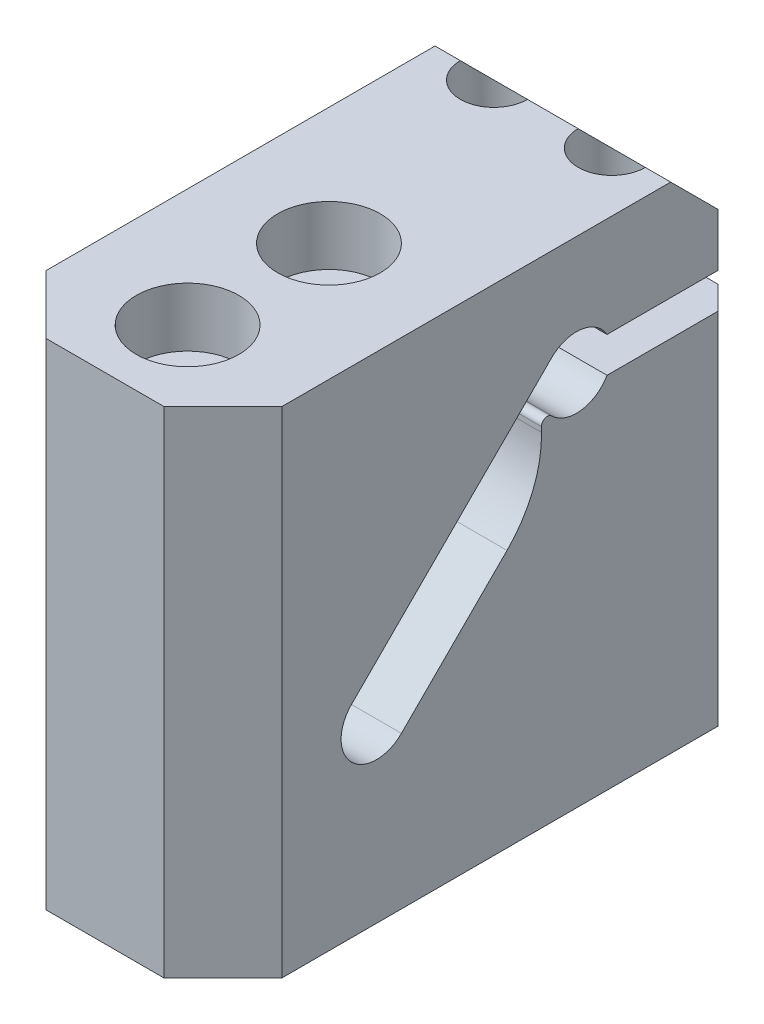
SolidWorks part; units mm, degrees
ref_plane "정면" through (0, 0, 0) normal (0, 0, 1) x (1, 0, 0)
ref_plane "윗면" through (0, 0, 0) normal (0, 1, 0) x (1, 0, 0)
ref_plane "우측면" through (0, 0, 0) normal (1, 0, 0) x (0, 0, -1)
sketch "스케치1" plane through (0, 0, 0) normal (1, 0, 0) x (0, 0, -1)
  line L0 (0, 0) -> (0, -32) construction
  line L1 (-19.0919, -14.8492) -> (-14.8492, -19.0919)
  line L2 (14, -32) -> (-30, -32)
  line L3 (14, -32) -> (14, 4)
  line L4 (8, 10) -> (-30, 10)
  line L5 (-30, -32) -> (-30, 10)
  line L6 (-19.0919, -14.8492) -> (-2.1213, 2.1213)
  line L7 (-14.8492, -19.0919) -> (2.1213, -2.1213)
  line L8 (-2.1213, 2.1213) -> (2.1213, -2.1213)
  line L9 (14, 4) -> (8, 10)
  line L10 (0, 0) -> (14, 0) construction
  line L11 (14, 1.5) -> (1, 1.5)
  line L12 (14, 1.5) -> (14, -1.5)
  line L13 (14, -1.5) -> (1, -1.5)
  line L14 (1, 1.5) -> (1, -1.5)
  line L15 (-3, 0) -> (-2.9035, -7.1461)
  circle A0 centre (0, 0) radius 3
  arc A1 (-19.0919, -14.8492) -> (-14.8492, -19.0919) centre (-16.9706, -16.9706) ccw
  point P6 (14, 10)
  dimension "D1" = 6
  dimension "D2" = 32
  dimension "D3" = 10
  dimension "D4" = 6
  dimension "D5" = 45
  dimension "D6" = 14
  dimension "D7" = 24
  dimension "D9" = 3
  dimension "D10" = 13
  dimension "D11" = 44
extrude "보스-돌출1" add sketch "스케치1" along normal blind 20 contours A1 L6 A0 L11 L3 L9 L4 L5 L2 L13 L7 | A0 L15 L7 region at (0, -19.522, 19.522) region at (0, -3.9996, 1.6249)
fillet "필렛1" radius 10 1 edges at (10, -7.1461, 2.9035)
fillet "필렛2" radius 0.5 1 edges at (10, -0.081, 2.9989)
sketch "스케치2" plane through (0, 10, 0) normal (0, 1, 0) x (1, 0, 0)
  line L0 (10, 14) -> (10, -30) construction
  line L1 (20, 14) -> (0, 14) construction
  line L2 (20, -30) -> (0, -30) construction
  circle A0 centre (10, -23) radius 4.35
  circle A1 centre (10, -11) radius 4.35
  circle A3 centre (5, 8) radius 1.5
  circle A4 centre (15, 8) radius 1.5
  circle A5 centre (5, 8) radius 2.85
  circle A6 centre (15, 8) radius 2.85
  circle A7 centre (10, -11) radius 2.5
  circle A8 centre (10, -23) radius 2.5
  point P18 (0, 0)
  line M11 (20, 8) -> (0, 8)
  dimension "D1" = 3
  dimension "D4" = 5.7
  dimension "D5" = 8.7
  dimension "D6" = 5
  dimension "D2" = 6
  dimension "D3" = 5
  dimension "D7" = 12
  dimension "D8" = 7
extrude "컷-돌출1" cut sketch "스케치2" against normal blind 5 contours L0 A1 A7 | A1 L0 A7 | A0 L0 A8 | L0 A0 A8 region at (13.0071, 10, 7.9929) region at (13.0071, 10, 19.9929) region at (9.9027, 10, 19.575) region at (9.9027, 10, 7.575)
extrude "컷-돌출2" cut sketch "스케치2<3>" against normal blind 5 contours A6 A4 M11 | A6 A4 M11 | A5 A3 M11 | A5 A3 M11 region at (7.175, 10, -7.9363) region at (5, 10, -9.5637) region at (15, 10, -10.7863) region at (12.825, 10, -7.9363)
sketch "스케치2<3>" plane through (0, 10, 0) normal (0, 1, 0) x (1, 0, 0) same geometry as "스케치2"
extrude "컷-돌출3" cut sketch "스케치2<4>" against normal through all contours A4 M11 | A4 M11 | A3 M11 | A3 M11 | L0 A7 | A7 L0 | A8 L0 | L0 A8 region at (11.061, 10, 11) region at (8.939, 10, 11) region at (15, 10, -7.3634) region at (15, 10, -8.6366) region at (5, 10, -8.6366) region at (5, 10, -7.3634) region at (11.061, 10, 23) region at (8.939, 10, 23)
sketch "스케치2<4>" plane through (0, 10, 0) normal (0, 1, 0) x (1, 0, 0) same geometry as "스케치2"
chamfer "모따기1" distance 5 angle 45 2 edges at (20, -11, 30) (0, -11, 30)
chamfer "모따기2" distance 2 angle 45 4 edges at (0, -16.75, -14) (0, 2.75, -14) (20, 2.75, -14) (20, -16.75, -14)
